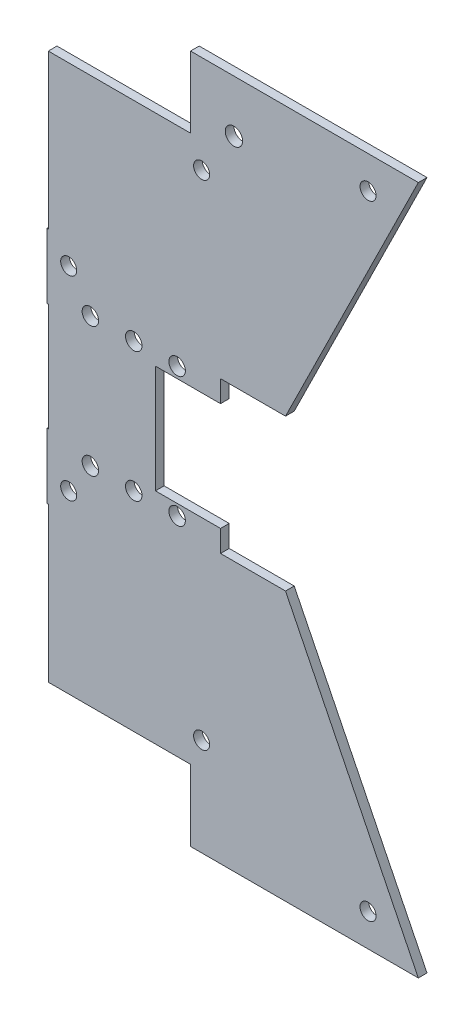
SolidWorks part; units mm, degrees
material "Thornel Mat VMA"
ref_plane "Front Plane" through (0, 0, 0) normal (0, 0, 1) x (1, 0, 0)
ref_plane "Top Plane" through (0, 0, 0) normal (0, 1, 0) x (1, 0, 0)
ref_plane "Right Plane" through (0, 0, 0) normal (1, 0, 0) x (0, 0, -1)
sketch "Sketch1" plane through (0, 0, 0) normal (0, 0, 1) x (1, 0, 0)
  line L0 (-2.9301, -104.5098) -> (-3.3149, -104.5098)
  line L1 (-3.3149, -72.8868) -> (-2.9301, -72.8868)
  line L78 (47.4851, -66.5368) -> (47.4851, -72.8868)
  line L79 (47.4851, -104.5098) -> (47.4851, -110.8598)
  line L80 (66.5174, -66.5368) -> (105.3971, 12.1397)
  line L81 (105.3971, 12.1397) -> (38.7094, 12.1397)
  line L88 (38.7094, 12.1397) -> (38.7094, -8.6883)
  line L89 (-2.9301, -8.6883) -> (38.7094, -8.6883)
  line L90 (-3.3149, -53.8368) -> (-2.9301, -53.8368)
  line L91 (-2.9301, -53.8368) -> (-2.9301, -8.6883)
  line L92 (-3.3149, -66.5368) -> (-3.3149, -53.8368)
  line L93 (-3.3149, -72.8868) -> (-3.3149, -66.5368)
  line L94 (-2.9301, -104.5098) -> (-2.9301, -72.8868)
  line L95 (-3.3149, -110.8598) -> (-3.3149, -104.5098)
  line L96 (66.5174, -110.8598) -> (105.3971, -189.5363)
  line L97 (105.3971, -189.5363) -> (38.7094, -189.5363)
  line L98 (38.7094, -189.5363) -> (38.7094, -168.7083)
  line L99 (-2.9301, -168.7083) -> (38.7094, -168.7083)
  line L106 (-3.3149, -110.8598) -> (-3.3149, -123.5598)
  line L107 (-3.3149, -123.5598) -> (-2.9301, -123.5598)
  line L108 (66.5174, -110.8598) -> (47.4851, -110.8598)
  line L109 (47.4851, -66.5368) -> (66.5174, -66.5368)
  line L110 (47.4851, -104.5098) -> (47.4851, -72.8868)
  line L111 (-2.9301, -123.5598) -> (-2.9301, -168.7083)
  circle A0 centre (90.6739, 2.6147) radius 2.3495
  circle A1 centre (41.9566, -16.4353) radius 2.3495
  circle A2 centre (3.0351, -60.1868) radius 2.3495
  circle A3 centre (3.0351, -117.2098) radius 2.3495
  circle A4 centre (41.9566, -160.9613) radius 2.3495
  circle A5 centre (90.6739, -180.0113) radius 2.3495
  circle A6 centre (51.4094, -3.1003) radius 2.54
  point P2 (90.6739, 2.6147)
  point P4 (41.9566, -16.4353)
  point P6 (3.0351, -60.1868)
  point P8 (3.0351, -117.2098)
  point P10 (41.9566, -160.9613)
  point P11 (90.6739, -180.0113)
  dimension "D2" = 4.699
  dimension "D5" = 5.08
  dimension "D1" = 66.6876
  dimension "D3" = 12.7
  dimension "D4" = 15.24
extrude "Boss-Extrude1" add sketch "Sketch1" along normal blind 2.54
sketch "Sketch2" plane through (0, 0, 2.54) normal (0, 0, 1) x (1, 0, 0)
  line L0 (-3.3149, -53.8368) -> (-3.3149, -72.8868) construction
  line L1 (47.4851, -66.5368) -> (66.5174, -66.5368) construction
  line L2 (47.4851, -88.6983) -> (-2.9301, -88.6983) construction
  line L3 (47.4851, -110.8598) -> (47.4851, -66.5368) construction
  line L4 (-2.9301, -72.8868) -> (-2.9301, -104.5098) construction
  circle A0 centre (9.3851, -69.7118) radius 2.413
  circle A1 centre (22.0851, -69.7118) radius 2.413
  circle A2 centre (34.7851, -69.7118) radius 2.413
  circle A4 centre (34.7851, -107.6848) radius 2.413
  circle A5 centre (22.0851, -107.6848) radius 2.413
  circle A6 centre (9.3851, -107.6848) radius 2.413
  dimension "D1" = 4.826
  dimension "D2" = 4.826
  dimension "D3" = 4.826
  dimension "D4" = 12.7
  dimension "D5" = 12.7
  dimension "D6" = 12.7
  dimension "D7" = 3.175
  dimension "D8" = 0
  dimension "D9" = 0
extrude "Cut-Extrude1" cut sketch "Sketch2" against normal through all
sketch "Sketch3" plane through (0, 0, 2.54) normal (0, 0, 1) x (1, 0, 0)
  line L0 (47.4851, -110.8598) -> (47.4851, -66.5368) construction
  line L1 (47.4851, -72.8868) -> (28.4351, -72.8868)
  line L2 (47.4851, -72.8868) -> (47.4851, -104.5098)
  line L3 (47.4851, -104.5098) -> (28.4351, -104.5098)
  line L4 (28.4351, -72.8868) -> (28.4351, -104.5098)
  line L5 (47.4851, -66.5368) -> (66.5174, -66.5368) construction
  line L6 (66.5174, -110.8598) -> (47.4851, -110.8598) construction
  circle A0 centre (22.0851, -69.7118) radius 2.413 construction
  dimension "D3" = 6.35
  dimension "D1" = 6.35
  dimension "D2" = 6.35
extrude "Cut-Extrude2" cut sketch "Sketch3" against normal through all
